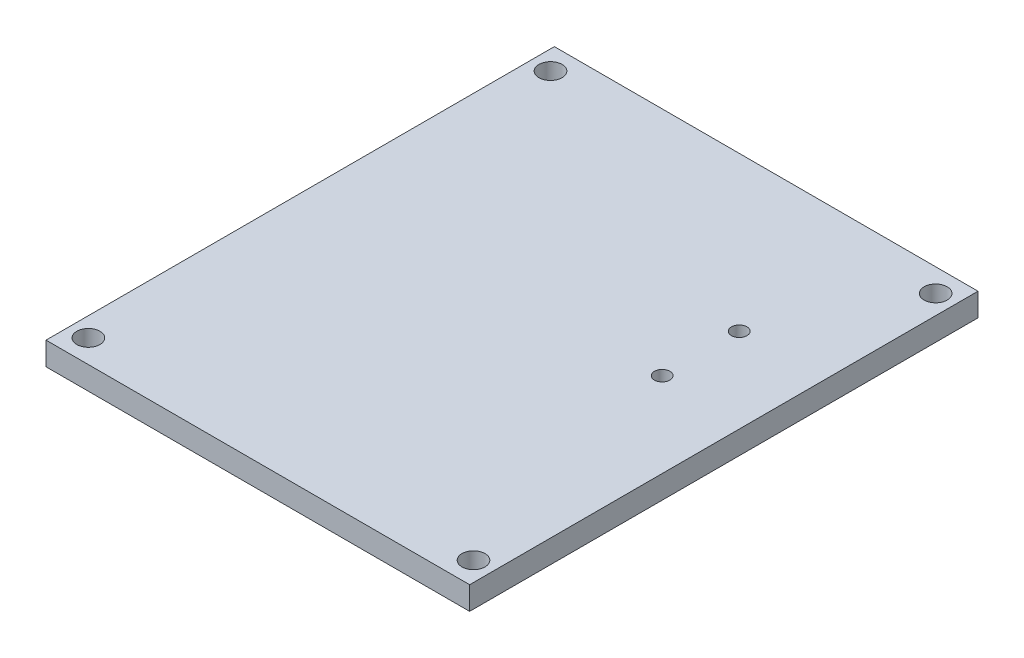
SolidWorks part; units mm, degrees
ref_plane "Plan de face" through (0, 0, 0) normal (0, 0, 1) x (1, 0, 0)
ref_plane "Plan de dessus" through (0, 0, 0) normal (0, 1, 0) x (1, 0, 0)
ref_plane "Plan de droite" through (0, 0, 0) normal (1, 0, 0) x (0, 0, -1)
sketch "Esquisse1" plane through (0, 0, 0) normal (0, 1, 0) x (1, 0, 0)
  line L0 (-27.5396, -33.0827) -> (27.4604, -33.0827)
  line L1 (-27.5396, -33.0827) -> (-27.5396, 32.9173)
  line L2 (-27.5396, 32.9173) -> (27.4604, 32.9173)
  line L3 (27.4604, -33.0827) -> (27.4604, 32.9173)
  line L4 (-27.5396, -33.0827) -> (27.4604, 32.9173) construction
  line L5 (-27.5396, 32.9173) -> (27.4604, -33.0827) construction
  line L6 (-25.0396, -30.0827) -> (24.9604, 29.9173) construction
  line L7 (-25.0396, 29.9173) -> (24.9604, -30.0827) construction
  line L8 (27.4604, 12.9173) -> (16.4604, 12.9173) construction
  line L9 (16.4604, 12.9173) -> (16.4604, 2.9173) construction
  line L10 (27.4604, 32.9173) -> (27.4604, 12.9173) construction
  circle A0 centre (-25.0396, 29.9173) radius 1.5
  circle A1 centre (24.9604, 29.9173) radius 1.5
  circle A2 centre (24.9604, -30.0827) radius 1.5
  circle A3 centre (-25.0396, -30.0827) radius 1.5
  circle A4 centre (16.4604, 12.9173) radius 1
  circle A5 centre (16.4604, 2.9173) radius 1
  point P0 (-0.0396, -0.0827)
  point P5 (-0.0396, -0.0827)
  dimension "D1" = 11
  dimension "D2" = 20
extrude "Boss.-Extru.1" add sketch "Esquisse1" along normal blind 3
